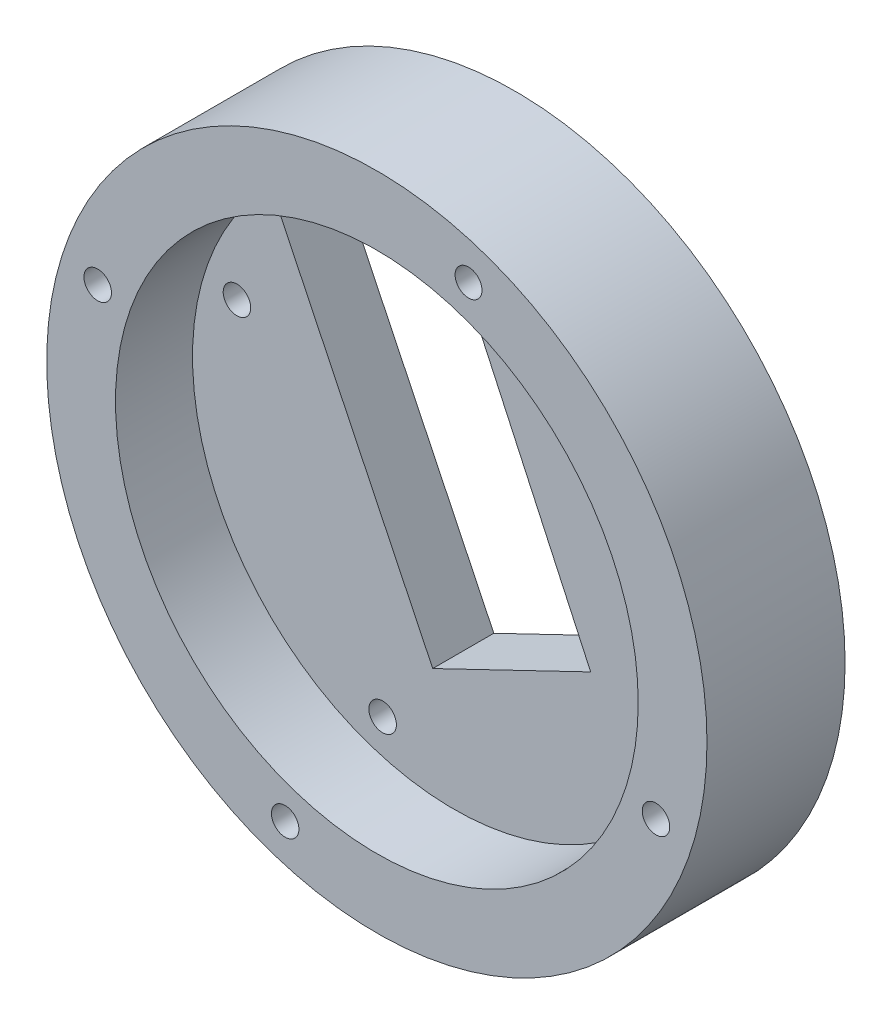
SolidWorks part; units mm, degrees
ref_plane "Front Plane" through (0, 0, 0) normal (0, 0, 1) x (1, 0, 0)
ref_plane "Top Plane" through (0, 0, 0) normal (0, 1, 0) x (1, 0, 0)
ref_plane "Right Plane" through (0, 0, 0) normal (1, 0, 0) x (0, 0, -1)
sketch "Sketch1" plane through (0, 0, 0) normal (0, 0, 1) x (1, 0, 0)
  circle A0 centre (0, 0) radius 60
  dimension "D1" = 120
extrude "Boss-Extrude1" add sketch "Sketch1" along normal blind 25.1
sketch "Sketch2" plane through (0, 0, 25.1) normal (0, 0, 1) x (1, 0, 0)
  circle A0 centre (-16.6647, -50.7331) radius 2.495
  circle A1 centre (-50.7331, 16.6647) radius 2.5
  circle A2 centre (16.6647, 50.7331) radius 2.4444
  circle A3 centre (50.7331, -16.6647) radius 2.5
sketch "Sketch3" plane through (0, 0, 25.1) normal (0, 0, 1) x (1, 0, 0)
  circle A0 centre (0, 0) radius 47.5
  dimension "D1" = 95
extrude "Cut-Extrude2" cut sketch "Sketch3" against normal blind 14
extrude "Cut-Extrude5" cut sketch "Sketch2" against normal through all both and the other way through all
sketch "Sketch6" plane through (0, 0, 0) normal (0, 0, -1) x (-1, 0, 0)
  circle A0 centre (11.9735, 47.2126) radius 3
  circle A1 centre (27.3813, 40.0293) radius 3
  circle A2 centre (-19.7177, -20.7629) radius 3
  circle A3 centre (-4.3099, -27.9462) radius 3
  dimension "D1" = 6
  dimension "D2" = 6
  dimension "D3" = 6
  dimension "D4" = 6
extrude "Cut-Extrude6" cut sketch "Sketch6" against normal blind 6
sketch "Sketch7" plane through (0, 0, 11.1) normal (0, 0, 1) x (1, 0, 0)
  line L0 (-32.7224, 32.7144) -> (-3.8455, -27.2733)
  line L1 (-3.8455, -27.2733) -> (24.8593, -13.4553)
  line L2 (24.8593, -13.4553) -> (-3.0425, 47.0016)
  line L3 (-3.0425, 47.0016) -> (-32.7224, 32.7144)
  circle A0 centre (0, 0) radius 47.1 construction
extrude "Cut-Extrude7" cut sketch "Sketch7" against normal through all both and the other way through all
sketch "Sketch8" plane through (0, 0, 0) normal (0, 0, -1) x (-1, 0, 0)
  circle A0 centre (-39.4274, -12.951) radius 2.5
  circle A1 centre (-12.951, 39.4274) radius 2.5
  circle A2 centre (39.4274, 12.951) radius 2.5
  circle A3 centre (12.951, -39.4274) radius 2.5
  point P20 (0, 0)
  dimension "D1" = 5
  dimension "D2" = 41.5
  dimension "D3" = 4
extrude "Cut-Extrude8" cut sketch "Sketch8" against normal blind 81
